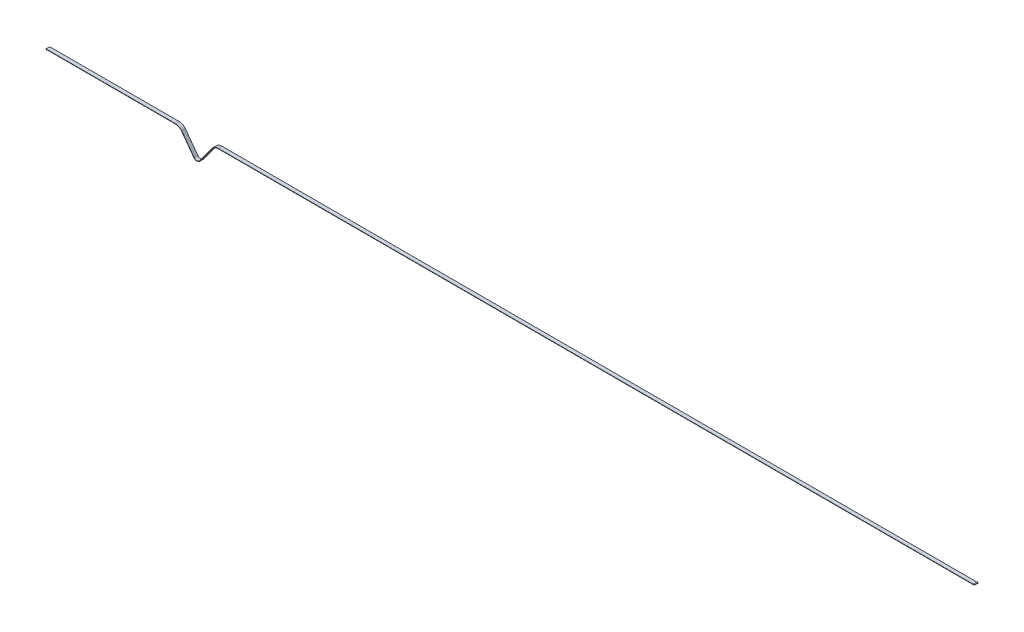
SolidWorks part; units mm, degrees
ref_plane "Front Plane" through (0, 0, 0) normal (0, 0, 1) x (1, 0, 0)
ref_plane "Top Plane" through (0, 0, 0) normal (0, 1, 0) x (1, 0, 0)
ref_plane "Right Plane" through (0, 0, 0) normal (1, 0, 0) x (0, 0, -1)
sketch "Sketch1" plane through (0, 0, 0) normal (1, 0, 0) x (0, 0, -1)
  line L1 (0, 0) -> (6, 0)
  line L2 (0, 0) -> (0, 0.63)
  line L3 (0, 0.63) -> (6, 0.63)
  line L4 (6, 0) -> (6, 0.63)
  dimension "D1" = 0.63
  dimension "D2" = 6
sketch "Sketch2" plane through (0, 0, 0) normal (0, 0, 1) x (1, 0, 0)
  line L0 (0, 0) -> (-1221.6046, 0)
  line L1 (-1231.2372, -4.8779) -> (-1251.2494, -32.1359)
  line L2 (-1261.0997, -32.1359) -> (-1281.1119, -4.8779)
  line L3 (-1290.7446, 0) -> (-1500, 0)
  arc A0 (-1221.6046, 0) -> (-1231.2372, -4.8779) centre (-1221.6046, -11.95) ccw
  arc A1 (-1251.2494, -32.1359) -> (-1261.0997, -32.1359) centre (-1256.1746, -28.52) cw
  arc A2 (-1281.1119, -4.8779) -> (-1290.7446, 0) centre (-1290.7446, -11.95) ccw
  circle A3 centre (-1290.7446, -11.95) radius 11.95 construction
  circle A4 centre (-1256.1746, -28.52) radius 6.11 construction
  circle A5 centre (-1221.6046, -11.95) radius 11.95 construction
  dimension "D1" = 6.11
  dimension "D4" = 1500
sweep "Sweep1" add profiles "Sketch1" path "Sketch2"
sketch "Sketch3" plane through (0, 0, 0) normal (0, 0, 1) x (1, 0, 0)
  line L0 (0, 0.63) -> (-1221.6046, 0.63) construction
  line L1 (-1.5, 0.63) -> (-1.5, 0)
  line L2 (0, 0) -> (-1221.6046, 0) construction
  line L3 (-1.5, 0) -> (0, 0)
  line L4 (0, 0) -> (0, 0.63)
  arc A1 (0, 0.63) -> (-1.5, 0.63) centre (-0.75, 0.63) ccw
  dimension "D1" = 0.75
extrude "Boss-Extrude1" add sketch "Sketch3" against normal through all
pattern_curve "CrvPattern1" [suppressed] of bodies 102 driven by "Sketch2" parameters "D1"=2000, "D3"=2, "D2"=1, "D4"=10
